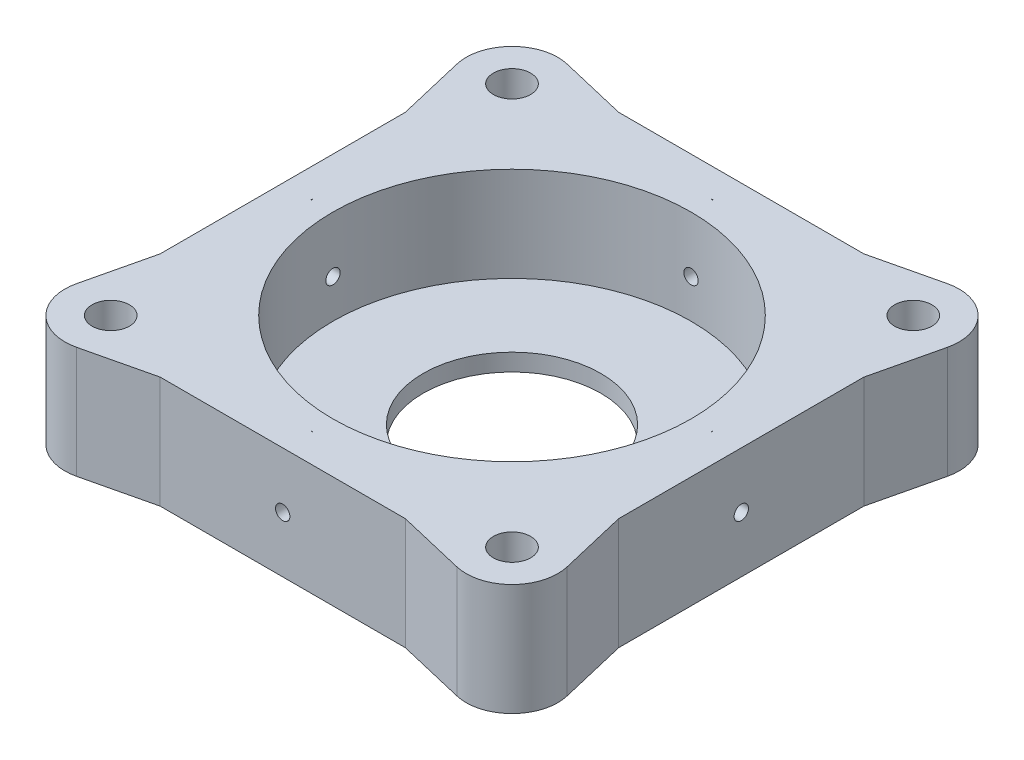
SolidWorks part; units mm, degrees
ref_plane "Front Plane" through (0, 0, 0) normal (0, 0, 1) x (1, 0, 0)
ref_plane "Top Plane" through (0, 0, 0) normal (0, 1, 0) x (1, 0, 0)
ref_plane "Right Plane" through (0, 0, 0) normal (1, 0, 0) x (0, 0, -1)
sketch "Sketch1" plane through (0, 0, 0) normal (0, 1, 0) x (1, 0, 0)
  line L0 (0, 35) -> (0, -35) construction
  line L1 (35, -35) -> (-35, -35)
  line L2 (35, -35) -> (35, 35)
  line L3 (35, 35) -> (-35, 35)
  line L4 (-35, -35) -> (-35, 35)
  line L5 (35, -35) -> (-35, 35) construction
  line L6 (35, 35) -> (-35, -35) construction
  line L7 (-35, 0) -> (35, 0) construction
  line L8 (-33.1578, 42.785) -> (7.8292, 33.0863)
  line L9 (-42.785, 33.1578) -> (-33.0863, -7.8292)
  line L10 (42.785, 33.1578) -> (33.0863, -7.8292)
  line L11 (33.1578, 42.785) -> (-7.8292, 33.0863)
  line L12 (-42.785, -33.1578) -> (-33.0863, 7.8292)
  line L13 (-33.1578, -42.785) -> (7.8292, -33.0863)
  line L14 (33.1578, -42.785) -> (-7.8292, -33.0863)
  line L15 (42.785, -33.1578) -> (33.0863, 7.8292)
  line L17 (40, -40) -> (-40, -40)
  line L18 (40, -40) -> (40, 40)
  line L19 (40, 40) -> (-40, 40)
  line L20 (-40, -40) -> (-40, 40)
  line L21 (40, -40) -> (-40, 40) construction
  line L22 (40, 40) -> (-40, -40) construction
  circle A0 centre (0, 0) radius 15.5
  circle A1 centre (0, 0) radius 34
  circle A2 centre (-35, 35) radius 3.25
  circle A3 centre (0, 0) radius 40
  circle A4 centre (-35, 35) radius 8
  circle A5 centre (35, 35) radius 3.25
  circle A6 centre (35, 35) radius 8
  circle A7 centre (-35, -35) radius 3.25
  circle A8 centre (-35, -35) radius 8
  circle A9 centre (35, -35) radius 3.25
  circle A10 centre (35, -35) radius 8
  dimension "D1" = 31
  dimension "D2" = 68
  dimension "D3" = 6.5
  dimension "D5" = 80
  dimension "D4" = 16
  dimension "D6" = 70
extrude "Boss-Extrude1" add sketch "Sketch1" along normal blind 19.5 contours L19 A4 L20 | L3 A4 L19 L20 L4 A2 | L4 A4 L3 A2 | A4 L9 L20 | A4 L20 L9 A3 L4 | A3 L9 L20 | L4 A3 L9 | L9 A3 L12 L4 | A3 L20 L12 | L12 A3 L4 | L20 A8 L4 A3 L12 | L12 A8 L20 | A8 L17 L20 | A8 L20 L17 L1 A7 L4 | A8 L4 A7 L1 | L4 A8 L1 A3 | L4 A3 L1 L13 L14 A1 L9 L12 | L3 A3 L4 L9 L12 A1 L11 L8 | A1 L12 L9 | A4 L4 A3 L3 | A4 L3 A3 L8 L19 | A4 L19 L8 | A3 L19 L8 | L8 A3 L3 | L11 A3 L8 L3 | A1 L8 L11 | L3 A3 L11 | L2 A3 L3 L11 L8 A1 L15 L10 | L3 A6 L19 L11 A3 | A3 L11 L19 | L19 A6 L11 | L2 A6 L3 A3 | A6 L2 A5 L3 | A6 L3 A5 L2 L18 L19 | A6 L19 L18 | L10 A6 L18 | L18 A6 L2 A3 L10 | A3 L18 L10 | L10 A3 L2 | L15 A3 L10 L2 | A3 L15 L18 | L2 A3 L15 | A1 L10 L15 | L1 A3 L2 L15 L10 A1 L13 L14 | A10 L18 L15 A3 L2 | A10 L15 L18 | A10 L2 A3 L1 | L18 A10 L2 A9 L1 L17 | L2 A10 L1 A9 | A10 L18 L17 | A10 L17 L14 | A10 L1 A3 L14 L17 | L14 A3 L1 | A3 L17 L14 | A3 L14 L1 L13 | A1 L14 L13 | L1 A3 L13 | A3 L13 L17 | L1 A8 L17 L13 A3 | L17 A8 L13 | A1 A0 region at (-27.625, 0, 37.5886) region at (-28.9419, 0, 28.9419) region at (-31.2062, 0, 31.2062) region at (-21.8672, 0, 37.555) region at (-24.6184, 0, 24.6184) region at (-10.9152, 0, 35.995) region at (-37.555, 0, 21.8672) region at (-30.8311, 0, 41.5907) region at (-27.2274, 0, 40.8217) region at (0, 0, 37.8149) region at (-35.995, 0, 10.9152) region at (-12.614, 0, 39.3478) region at (-40.8217, 0, 27.2274) region at (24.6184, 0, 24.6184) region at (10.9152, 0, 35.995) region at (0, 0, 34.191) region at (-37.8149, 0, 0) region at (-39.3478, 0, 12.614) region at (12.614, 0, 39.3478) region at (28.9419, 0, 28.9419) region at (21.8672, 0, 37.555) region at (0, 0, 33.0383) region at (-35.995, 0, -10.9152) region at (-24.6184, 0, -24.6184) region at (-34.191, 0, 0) region at (-39.3478, 0, -12.614) region at (27.2274, 0, 40.8217) region at (31.2062, 0, 31.2062) region at (29.375, 0, 35.1838) region at (37.555, 0, 21.8672) region at (35.995, 0, 10.9152) region at (34.191, 0, 0) region at (-37.555, 0, -21.8672) region at (-28.9419, 0, -28.9419) region at (-40.8217, 0, -27.2274) region at (30.8311, 0, 41.5907) region at (37.8149, 0, 0) region at (39.3478, 0, 12.614) region at (24.6184, 0, -24.6184) region at (-37.5886, 0, -27.625) region at (-31.2062, 0, -31.2062) region at (-10.9152, 0, -35.995) region at (-21.8672, 0, -37.555) region at (0, 0, -34.191) region at (-40.5144, 0, -40.5144) region at (40.8217, 0, 27.2274) region at (35.995, 0, -10.9152) region at (39.3478, 0, -12.614) region at (0, 0, -37.8149) region at (-12.614, 0, -39.3478) region at (-27.2274, 0, -40.8217) region at (28.9419, 0, -28.9419) region at (37.555, 0, -21.8672) region at (40.8217, 0, -27.2274) region at (10.9152, 0, -35.995) region at (12.614, 0, -39.3478) region at (31.2062, 0, -31.2062) region at (35.1838, 0, -29.375) region at (21.8672, 0, -37.555) region at (41.5907, 0, -30.8311)
sketch "Sketch2" plane through (0, 19.5, 0) normal (0, 1, 0) x (1, 0, 0)
  circle A0 centre (0, 0) radius 31.25
  dimension "D1" = 62.5
extrude "Cut-Extrude1" cut sketch "Sketch2" against normal blind 16.5
sketch "Sketch3" plane through (0, 0, 0) normal (0, -1, 0) x (1, 0, 0)
  circle A0 centre (-35, 35) radius 5.25
  circle A1 centre (35, 35) radius 5.25
  circle A2 centre (35, -35) radius 5.25
  circle A3 centre (-35, -35) radius 5.25
  dimension "D1" = 10.5
extrude "Cut-Extrude2" cut sketch "Sketch3" against normal blind 10
sketch "Sketch4" plane through (0, 0, 40) normal (0, 0, 1) x (1, 0, 0)
  line L0 (0, 0) -> (0, 19.5) construction
  line L1 (21.3883, 0) -> (-21.3883, 0) construction
  line L2 (21.3883, 19.5) -> (-21.3883, 19.5) construction
  circle A0 centre (0, 9.75) radius 1.25
  dimension "D1" = 2.5
extrude "Cut-Extrude3" cut sketch "Sketch4" against normal up to surface (80 mm away) up to face at (0, 9.75, -40)
sketch "Sketch5" plane through (40, 0, 0) normal (1, 0, 0) x (0, 0, -1)
  line L0 (0, 0) -> (0, 19.5) construction
  line L1 (-21.3883, 19.5) -> (21.3883, 19.5) construction
  circle A0 centre (0, 9.75) radius 1.25
  dimension "D1" = 2.5
extrude "Cut-Extrude4" cut sketch "Sketch5" against normal up to surface (80 mm away) up to face at (-40, 9.75, 0)
sketch "Sketch6" [suppressed] plane through (0, 19.5, 0) normal (0, 1, 0) x (1, 0, 0)
  line L12 (21.3883, -40) -> (33.1578, -42.785)
  line L13 (42.785, -33.1578) -> (40, -21.3883)
  line L14 (40, -21.3883) -> (40, 21.3883)
  line L15 (40, 21.3883) -> (42.785, 33.1578)
  line L16 (33.1578, 42.785) -> (21.3883, 40)
  line L17 (21.3883, 40) -> (-21.3883, 40)
  line L18 (-21.3883, 40) -> (-33.1578, 42.785)
  line L19 (-42.785, 33.1578) -> (-40, 21.3883)
  line L20 (-40, 21.3883) -> (-40, -21.3883)
  line L21 (-40, -21.3883) -> (-42.785, -33.1578)
  line L22 (-33.1578, -42.785) -> (-21.3883, -40)
  line L23 (-21.3883, -40) -> (21.3883, -40)
  line L24 (21.3883, -40) -> (33.1578, -42.785)
  line L25 (42.785, -33.1578) -> (40, -21.3883)
  line L26 (40, -21.3883) -> (40, 21.3883)
  line L27 (40, 21.3883) -> (42.785, 33.1578)
  line L28 (33.1578, 42.785) -> (21.3883, 40)
  line L29 (21.3883, 40) -> (-21.3883, 40)
  line L30 (-21.3883, 40) -> (-33.1578, 42.785)
  line L31 (-42.785, 33.1578) -> (-40, 21.3883)
  line L32 (-40, 21.3883) -> (-40, -21.3883)
  line L33 (-40, -21.3883) -> (-42.785, -33.1578)
  line L34 (-33.1578, -42.785) -> (-21.3883, -40)
  line L35 (-21.3883, -40) -> (21.3883, -40)
  circle A0 centre (0, 0) radius 31.25 construction
  circle A1 centre (35, 35) radius 3.25 construction
  circle A2 centre (-35, 35) radius 3.25 construction
  circle A3 centre (35, -35) radius 3.25 construction
  arc A4 (33.1578, -42.785) -> (42.785, -33.1578) centre (35, -35) ccw
  arc A5 (42.785, 33.1578) -> (33.1578, 42.785) centre (35, 35) ccw
  arc A6 (-33.1578, 42.785) -> (-42.785, 33.1578) centre (-35, 35) ccw
  arc A7 (-42.785, -33.1578) -> (-33.1578, -42.785) centre (-35, -35) ccw
  arc A8 (33.1578, -42.785) -> (42.785, -33.1578) centre (35, -35) ccw
  arc A9 (42.785, 33.1578) -> (33.1578, 42.785) centre (35, 35) ccw
  arc A10 (-33.1578, 42.785) -> (-42.785, 33.1578) centre (-35, 35) ccw
  arc A11 (-42.785, -33.1578) -> (-33.1578, -42.785) centre (-35, -35) ccw
  circle A12 centre (-35, -35) radius 3.25 construction
  circle A13 centre (0, 0) radius 31.25
  circle A14 centre (35, 35) radius 3.25
  circle A15 centre (-35, 35) radius 3.25
  circle A16 centre (35, -35) radius 3.25
  circle A17 centre (-35, -35) radius 3.25
  dimension "D1" = 0
extrude "Boss-Extrude4" [suppressed] add sketch "Sketch6" along normal blind 3.5
sketch "Sketch7" [suppressed] plane through (0, 0, 0) normal (0, -1, 0) x (1, 0, 0)
  line L0 (-35, 35) -> (-38.7123, 38.7123) construction
  line L1 (-29.1444, 33.431) -> (-30.7134, 39.2866)
  line L2 (-30.7134, 39.2866) -> (-36.569, 40.8556)
  line L3 (-36.569, 40.8556) -> (-40.8556, 36.569)
  line L4 (-40.8556, 36.569) -> (-39.2866, 30.7134)
  line L5 (-39.2866, 30.7134) -> (-33.431, 29.1444)
  line L6 (-33.431, 29.1444) -> (-29.1444, 33.431)
  line L7 (39.2866, 30.7134) -> (40.8556, 36.569)
  line L8 (40.8556, 36.569) -> (36.569, 40.8556)
  line L9 (36.569, 40.8556) -> (30.7134, 39.2866)
  line L10 (30.7134, 39.2866) -> (29.1444, 33.431)
  line L11 (29.1444, 33.431) -> (33.431, 29.1444)
  line L12 (33.431, 29.1444) -> (39.2866, 30.7134)
  line L13 (30.7134, -39.2866) -> (36.569, -40.8556)
  line L14 (36.569, -40.8556) -> (40.8556, -36.569)
  line L15 (40.8556, -36.569) -> (39.2866, -30.7134)
  line L16 (39.2866, -30.7134) -> (33.431, -29.1444)
  line L17 (33.431, -29.1444) -> (29.1444, -33.431)
  line L18 (29.1444, -33.431) -> (30.7134, -39.2866)
  line L19 (-39.2866, -30.7134) -> (-40.8556, -36.569)
  line L20 (-40.8556, -36.569) -> (-36.569, -40.8556)
  line L21 (-36.569, -40.8556) -> (-30.7134, -39.2866)
  line L22 (-30.7134, -39.2866) -> (-29.1444, -33.431)
  line L23 (-29.1444, -33.431) -> (-33.431, -29.1444)
  line L24 (-33.431, -29.1444) -> (-39.2866, -30.7134)
  line L25 (0, 40) -> (0, -40) construction
  line L26 (21.3883, 40) -> (-21.3883, 40) construction
  line L27 (21.3883, -40) -> (-21.3883, -40) construction
  circle A0 centre (-35, 35) radius 5.25 construction
  point P32 (0, 0)
  dimension "D1" = 10.5
  dimension "D2" = 4
extrude "Cut-Extrude5" [suppressed] cut sketch "Sketch7" against normal offset from surface (21.5 mm away) 1.5 up to face at (35, 0, 29.75)
